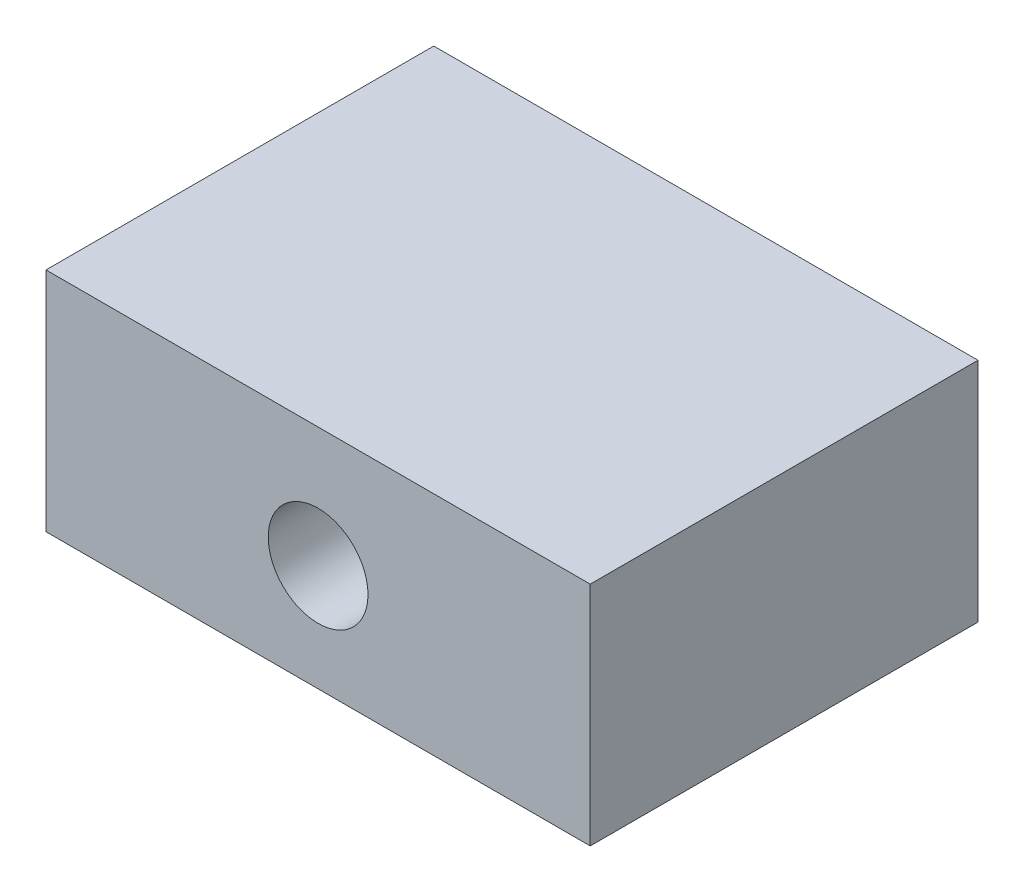
SolidWorks part; units mm, degrees
ref_plane "Płaszczyzna przednia" through (0, 0, 0) normal (0, 0, 1) x (1, 0, 0)
ref_plane "Płaszczyzna górna" through (0, 0, 0) normal (0, 1, 0) x (1, 0, 0)
ref_plane "Płaszczyzna prawa" through (0, 0, 0) normal (1, 0, 0) x (0, 0, -1)
sketch "Szkic1" plane through (0, 0, 0) normal (0, 0, 1) x (1, 0, 0)
  line L1 (-6, -2.5) -> (6, -2.5)
  line L2 (-6, -2.5) -> (-6, 2.5)
  line L3 (-6, 2.5) -> (6, 2.5)
  line L4 (6, -2.5) -> (6, 2.5)
  line L5 (-6, -2.5) -> (6, 2.5) construction
  line L6 (-6, 2.5) -> (6, -2.5) construction
  point P0 (0, 0)
  dimension "D1" = 12
  dimension "D2" = 5
extrude "Dodanie-wyciągnięcie1" add sketch "Szkic1" along normal blind 8.55
sketch "Szkic2" plane through (0, 0, 8.55) normal (0, 0, 1) x (1, 0, 0)
  line L1 (6, 2.5) -> (-6, 2.5) construction
  circle A1 centre (0, -0.15) radius 1.1
  dimension "D1" = 2.2
  dimension "D2" = 2.65
extrude "Wytnij-wyciągnięcie1" cut sketch "Szkic2" against normal through all
